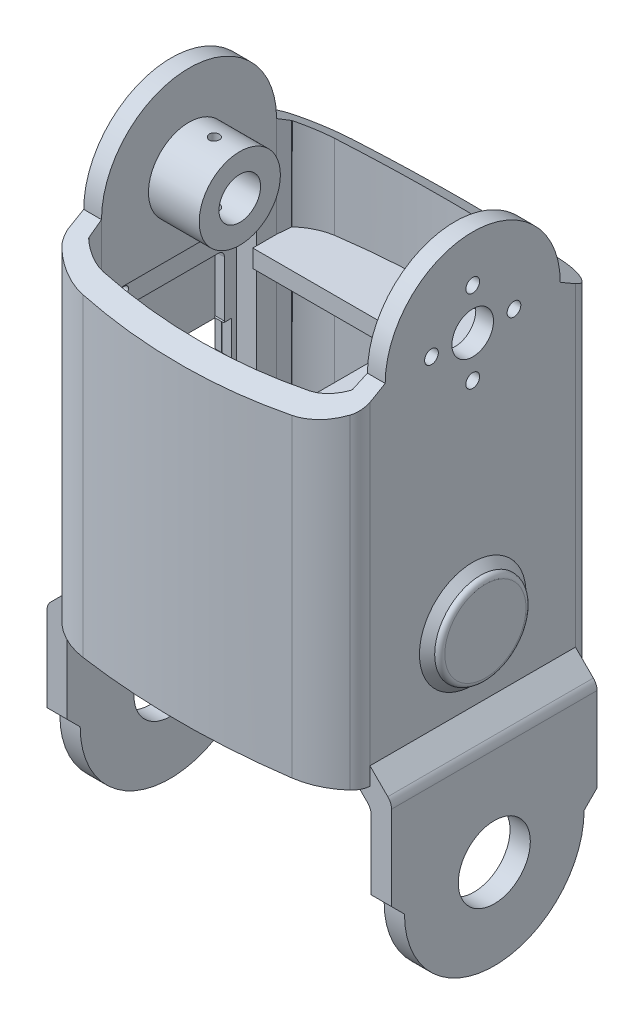
SolidWorks part; units mm, degrees
material "PLA"
ref_plane "Front Plane" through (0, 0, 0) normal (0, 0, 1) x (1, 0, 0)
ref_plane "Top Plane" through (0, 0, 0) normal (0, 1, 0) x (1, 0, 0)
ref_plane "Right Plane" through (0, 0, 0) normal (1, 0, 0) x (0, 0, -1)
sketch "Sketch1" plane through (0, 0, 0) normal (1, 0, 0) x (0, 0, -1)
  line L0 (-17.25, 0) -> (-17.25, -67.25)
  line L1 (17.25, 0) -> (17.25, -67.25)
  line L2 (-17.25, -67.25) -> (17.25, -67.25)
  arc A0 (17.25, 0) -> (-17.25, 0) centre (0, 0) ccw
  circle A1 centre (0, 0) radius 4.1
  circle A2 centre (0, 0) radius 8.125 construction
  circle A3 centre (0, 8.125) radius 1.35
  circle A4 centre (8.125, 0) radius 1.35
  circle A5 centre (-8.125, 0) radius 1.35
  circle A6 centre (0, -8.125) radius 1.35
  dimension "D1" = 34.5
  dimension "D4" = 8.2
  dimension "D5" = 16.25
  dimension "D6" = 2.7
  dimension "D2" = 67.25
  dimension "D3" = 67.25
extrude "Boss-Extrude1" add sketch "Sketch1" along normal blind 3.5
ref_plane "Plane1" through (0, 0, 0) normal (0, -1, 0) x (-1, 0, 0)
ref_plane "Plane2" through (29.7, 0, 0) normal (-1, 0, 0) x (0, 0, 1)
sketch "Sketch2" plane through (0, 0, 0) normal (0, -1, 0) x (-1, 0, 0)
  line L0 (0, -17.25) -> (-59.4, -17.25) construction
  line L1 (-29.7, 0) -> (-29.7, -28) construction
  line L3 (-59.4, -17.25) -> (-59.4, -20.25)
  line L4 (0, -17.25) -> (0, -20.25)
  line L6 (-29.7, -28) -> (-17.6897, -27.7644) construction
  line L7 (-17.6897, -27.7644) -> (-9.1109, -26.529) construction
  line L8 (-9.1109, -26.529) -> (-3.2086, -24.1613) construction
  line L9 (-3.2086, -24.1613) -> (-1.3201, -22.8861) construction
  line L10 (-1.3201, -22.8861) -> (-0.3051, -21.5079) construction
  line L11 (-0.3051, -21.5079) -> (-0.1375, -21.1541) construction
  line L12 (-0.1375, -21.1541) -> (0, -20.25) construction
  line L13 (-3.5, -17.25) -> (-3.7359, -19.9547)
  line L14 (-55.9, -17.25) -> (-55.6641, -19.9547)
  line L15 (-55.9, -17.25) -> (-59.4, -17.25)
  line L17 (0, -17.25) -> (-3.5, -17.25)
  arc A0 (0, -20.25) -> (-1.3201, -22.8861) centre (-4.0147, -19.8881) cw
  arc A1 (-1.3201, -22.8861) -> (-9.1109, -26.529) centre (-11.2153, -11.8765) cw
  arc A2 (-29.7, -28) -> (-9.1109, -26.529) centre (-29.7, 116.8281) ccw
  arc A3 (-29.7, -24.2523) -> (-9.3648, -22.779) centre (-29.7, 116.8281) ccw
  arc A4 (-3.8286, -20.1061) -> (-9.3648, -22.779) centre (-11.2153, -11.8765) cw
  arc A5 (-3.7359, -19.9547) -> (-3.8286, -20.1061) centre (-4.0147, -19.8881) cw
  arc A6 (-29.7, -28) -> (-50.2891, -26.529) centre (-29.7, 116.8281) cw
  arc A7 (-58.0799, -22.8861) -> (-50.2891, -26.529) centre (-48.1847, -11.8765) ccw
  arc A8 (-59.4, -20.25) -> (-58.0799, -22.8861) centre (-55.3853, -19.8881) ccw
  arc A9 (-55.6641, -19.9547) -> (-55.5714, -20.1061) centre (-55.3853, -19.8881) ccw
  arc A10 (-55.5714, -20.1061) -> (-50.0352, -22.779) centre (-48.1847, -11.8765) ccw
  arc A11 (-29.7, -24.2523) -> (-50.0352, -22.779) centre (-29.7, 116.8281) cw
  dimension "D1" = 59.4
extrude "Boss-Extrude2" add sketch "Sketch2" along normal blind 67.25
mirror "Mirror2" about plane through (29.7, 0, 0) normal (-1, 0, 0) of "Boss-Extrude1"
sketch "Sketch3" plane through (0, 0, 0) normal (-1, 0, 0) x (0, 0, 1)
  line L0 (17.25, 0) -> (32.7486, -8.9481)
  line L1 (-1.925, 0) -> (1.925, 0) construction
  line L2 (32.7486, -8.9481) -> (32.7486, 0)
  line L3 (32.7486, 0) -> (17.25, 0)
  arc A0 (17.25, 0) -> (-17.25, 0) centre (0, 0) ccw construction
  dimension "D1" = 30
extrude "Cut-Extrude1" cut sketch "Sketch3" against normal through all
ref_plane "Plane3" through (0, 0, 0) normal (0, 0, -1) x (-1, 0, 0)
mirror "Mirror3" about plane through (0, 0, 0) normal (0, 0, -1) of "Cut-Extrude1", "Boss-Extrude2"
sketch "Sketch4" plane through (0, 0, 0) normal (-1, 0, 0) x (0, 0, 1)
  line L0 (-20.25, -67.25) -> (-20.25, -1.7321) construction
  line L1 (-13.25, -13.5) -> (13.25, -13.5)
  line L2 (-13.25, -13.5) -> (-13.25, -60.75)
  line L3 (-13.25, -60.75) -> (13.25, -60.75)
  line L4 (13.25, -13.5) -> (13.25, -60.75)
  line L5 (20.25, -67.25) -> (20.25, -1.7321) construction
  line L6 (20.25, -67.25) -> (-20.25, -67.25) construction
  dimension "D1" = 7
  dimension "D2" = 7
  dimension "D3" = 13.5
  dimension "D4" = 6.5
extrude "Cut-Extrude2" cut sketch "Sketch4" against normal blind 3.5
sketch "Sketch6" plane through (0, 0, 0) normal (-1, 0, 0) x (0, 0, 1)
  line L8 (-15.75, -63.25) -> (15.75, -63.25)
  line L9 (-15.75, -11) -> (-15.75, -63.25)
  line L10 (15.75, -63.25) -> (15.75, -11)
  line L11 (15.75, -11) -> (-15.75, -11)
  line L12 (-15.75, -63.25) -> (15.75, -63.25)
  line L13 (-15.75, -11) -> (-15.75, -63.25)
  line L14 (15.75, -63.25) -> (15.75, -11)
  line L15 (15.75, -11) -> (-15.75, -11)
  dimension "D1" = 2.5
extrude "Boss-Extrude3" add sketch "Sketch6" along normal blind 2
chamfer "Chamfer2" distance 2 angle 45 4 edges at (-2, -63.25, 0) (-2, -37.125, 15.75) (-2, -37.125, -15.75) (-2, -11, 0)
sketch "Sketch7" plane through (0, 0, 0) normal (1, 0, 0) x (0, 0, -1)
  line L4 (-13.25, -60.75) -> (13.25, -60.75)
  line L5 (13.25, -60.75) -> (13.25, -13.5)
  line L6 (13.25, -13.5) -> (-13.25, -13.5)
  line L7 (-13.25, -13.5) -> (-13.25, -60.75)
  line L8 (-13.25, -60.75) -> (13.25, -60.75)
  line L9 (13.25, -60.75) -> (13.25, -13.5)
  line L10 (13.25, -13.5) -> (-13.25, -13.5)
  line L11 (-13.25, -13.5) -> (-13.25, -60.75)
  dimension "D1" = 0
extrude "Cut-Extrude3" cut sketch "Sketch7" against normal blind 0.8
sketch "Sketch8" plane through (-2, 0, 0) normal (-1, 0, 0) x (0, 0, 1)
  line L0 (15.75, -63.25) -> (15.75, -11) construction
  line L1 (-10.6511, -32.25) -> (10.75, -32.25)
  line L2 (-10.6511, -32.25) -> (-10.6511, -38.75)
  line L3 (-10.6511, -38.75) -> (10.75, -38.75)
  line L4 (10.75, -32.25) -> (10.75, -38.75)
  line L5 (-15.75, -11) -> (-15.75, -63.25) construction
  line L6 (15.75, -11) -> (-15.75, -11) construction
  line L7 (-15.75, -63.25) -> (15.75, -63.25) construction
  dimension "D1" = 5
  dimension "D2" = 5.0989
  dimension "D3" = 21.25
  dimension "D4" = 24.5
extrude "Cut-Extrude4" cut sketch "Sketch8" against normal up to next
sketch "Sketch9" plane through (59.4, 0, 0) normal (1, 0, 0) x (0, 0, -1)
  circle A0 centre (0, -49.64) radius 7.1
  dimension "D1" = 14.2
extrude "Cut-Extrude5" cut sketch "Sketch9" against normal up to next
ref_plane "Plane4" through (0, -19.75, 0) normal (0, -1, 0) x (-1, 0, 0)
sketch "Sketch10" plane through (0, -19.75, 0) normal (0, -1, 0) x (-1, 0, 0)
  line L0 (-55.6641, -19.9547) -> (-55.9, -17.25) construction
  line L1 (-3.5, -17.25) -> (-3.7359, -19.9547) construction
  line L3 (-3.5, -17.25) -> (-3.5, 17.25) construction
  line L6 (-3.5, 17.25) -> (-3.7359, 19.9547) construction
  line L7 (-55.9, -17.25) -> (-55.9, 17.25) construction
  line L8 (-55.6641, 19.9547) -> (-55.9, 17.25) construction
  line L9 (-55.6641, -19.9547) -> (-55.9, -17.25)
  line L10 (-3.5, -17.25) -> (-3.7359, -19.9547)
  line L11 (-3.5, -17.25) -> (-3.5, -12.56)
  line L12 (-3.5, 17.25) -> (-3.7359, 19.9547)
  line L13 (-55.9, -17.25) -> (-55.9, 17.25)
  line L14 (-55.6641, 19.9547) -> (-55.9, 17.25)
  line L15 (-18.2613, -12.36) -> (-18.2613, -12.56) construction
  line L16 (-12.72, -12.36) -> (-25.62, -12.36) construction
  line L17 (-3.5, -12.56) -> (-34.52, -12.56)
  line L18 (-34.52, -12.56) -> (-34.52, 12.56)
  line L19 (-3.5, 12.56) -> (-3.5, 17.25)
  line L43 (-34.52, 12.56) -> (-3.5, 12.56)
  line L45 (-25.62, 12.36) -> (-12.72, 12.36) construction
  line L46 (-34.52, 5) -> (-34.52, 13.1992) construction
  line L47 (-31.62, 5) -> (-35.82, 5) construction
  line L48 (-34.32, 6.7) -> (-34.32, 5.6557) construction
  arc A0 (-55.6641, -19.9547) -> (-55.5714, -20.1061) centre (-55.3853, -19.8881) ccw construction
  arc A1 (-50.0352, -22.779) -> (-9.3648, -22.779) centre (-29.7, 116.8281) ccw construction
  arc A2 (-55.5714, -20.1061) -> (-50.0352, -22.779) centre (-48.1847, -11.8765) ccw construction
  arc A3 (-9.3648, -22.779) -> (-3.8286, -20.1061) centre (-11.2153, -11.8765) ccw construction
  arc A4 (-3.8286, -20.1061) -> (-3.7359, -19.9547) centre (-4.0147, -19.8881) ccw construction
  arc A5 (-3.7359, 19.9547) -> (-3.8286, 20.1061) centre (-4.0147, 19.8881) ccw construction
  arc A6 (-3.8286, 20.1061) -> (-9.3648, 22.779) centre (-11.2153, 11.8765) ccw construction
  arc A7 (-9.3648, 22.779) -> (-50.0352, 22.779) centre (-29.7, -116.8281) ccw construction
  arc A8 (-55.5714, 20.1061) -> (-55.6641, 19.9547) centre (-55.3853, 19.8881) ccw construction
  arc A9 (-50.0352, 22.779) -> (-55.5714, 20.1061) centre (-48.1847, 11.8765) ccw construction
  arc A30 (-55.6641, -19.9547) -> (-55.5714, -20.1061) centre (-55.3853, -19.8881) ccw
  arc A31 (-50.0352, -22.779) -> (-9.3648, -22.779) centre (-29.7, 116.8281) ccw
  arc A32 (-55.5714, -20.1061) -> (-50.0352, -22.779) centre (-48.1847, -11.8765) ccw
  arc A33 (-9.3648, -22.779) -> (-3.8286, -20.1061) centre (-11.2153, -11.8765) ccw
  arc A34 (-3.8286, -20.1061) -> (-3.7359, -19.9547) centre (-4.0147, -19.8881) ccw
  arc A35 (-3.7359, 19.9547) -> (-3.8286, 20.1061) centre (-4.0147, 19.8881) ccw
  arc A36 (-3.8286, 20.1061) -> (-9.3648, 22.779) centre (-11.2153, 11.8765) ccw
  arc A37 (-9.3648, 22.779) -> (-50.0352, 22.779) centre (-29.7, -116.8281) ccw
  arc A38 (-55.5714, 20.1061) -> (-55.6641, 19.9547) centre (-55.3853, 19.8881) ccw
  arc A39 (-50.0352, 22.779) -> (-55.5714, 20.1061) centre (-48.1847, 11.8765) ccw
  dimension "D1" = 0.2
  dimension "D2" = 0.2
  dimension "D3" = 0.2
extrude "Boss-Extrude4" add sketch "Sketch10" along normal blind 3.5
sketch "Sketch11" plane through (0, -23.25, 0) normal (0, -1, 0) x (-1, 0, 0)
  line L0 (-36.07, -6.9) -> (-40.07, -6.9) construction
  line L2 (-36.07, -6.9) -> (-36.07, -24.1084) construction
  line L3 (-40.07, -6.9) -> (-40.07, -24.1084) construction
  line L5 (-36.07, -24.1084) -> (-40.07, -24.1084)
  line L6 (-36.07, -24.1084) -> (-36.07, 25.609)
  line L7 (-36.07, 25.609) -> (-40.07, 25.609)
  line L8 (-40.07, -24.1084) -> (-40.07, 25.609)
  arc A0 (-50.0352, -22.779) -> (-9.3648, -22.779) centre (-29.7, 116.8281) ccw construction
  dimension "D1" = 4
extrude "Boss-Extrude5" add sketch "Sketch11" along normal blind 40
sketch "Sketch12" plane through (40.07, 0, 0) normal (1, 0, 0) x (0, 0, -1)
  circle A0 centre (0, -49.64) radius 7.1
extrude "Cut-Extrude6" cut sketch "Sketch12" against normal blind 10
chamfer "Chamfer3" distance 1 angle 45 1 edges at (36.07, -23.25, 0)
chamfer "Chamfer4" distance 1 angle 45 1 edges at (40.07, -23.25, 0)
fillet "Fillet1" radius 3 2 edges at (38.0708, -63.25, -24.0037) (38.0708, -63.25, 24.0037)
sketch "Sketch13" plane through (59.4, 0, 0) normal (1, 0, 0) x (0, 0, -1)
  circle A0 centre (0, -49.64) radius 9
  circle A1 centre (0, -49.64) radius 5.5
  dimension "D1" = 18
  dimension "D2" = 11
extrude "Boss-Extrude6" add sketch "Sketch13" along normal blind 1.5
sketch "Sketch16" plane through (60.9, 0, 0) normal (1, 0, 0) x (0, 0, -1)
  circle A0 centre (0, -49.64) radius 9
extrude "Boss-Extrude7" add sketch "Sketch16" along normal blind 1
fillet "Fillet2" radius 1 1 edges at (61.9, -49.64, -9)
ref_plane "Plane5" through (0, 0, 20.25) normal (0, 0, -1) x (-1, 0, 0)
sketch "Sketch17" plane through (0, 0, 20.25) normal (0, 0, -1) x (-1, 0, 0)
  line L0 (-59.4, -67.25) -> (-55.9, -67.25) construction
  line L1 (-59.4, -67.25) -> (-59.4, -70.75) construction
  line L3 (-55.9, -67.25) -> (-59.4, -70.75) construction
  line L4 (-59.4, -67.25) -> (-59.65, -67.25) construction
  line L5 (-59.4, -70.75) -> (-59.65, -71) construction
  line L6 (-59.65, -71) -> (-59.65, -105.91) construction
  line L7 (-59.4, -67.25) -> (-59.4, -63.75) construction
  line L8 (-59.4, -63.75) -> (-64.5645, -68.9145) construction
  line L9 (-59.65, -105.91) -> (-63.15, -105.91)
  line L10 (-63.15, -105.91) -> (-63.15, -67.5)
  line L11 (-63.15, -67.5) -> (-59.4, -63.75)
  line L12 (-59.4, -63.75) -> (-59.4, -67.25)
  line L13 (-59.4, -67.25) -> (-55.9, -67.25)
  line L14 (-55.9, -67.25) -> (-59.65, -71)
  line L15 (-59.65, -71) -> (-59.65, -105.91)
  dimension "D1" = 3.5
  dimension "D2" = 3.5
  dimension "D3" = 0.25
  dimension "D4" = 3.5
  dimension "D5" = 45
  dimension "D6" = 3.5
sketch "Sketch18" plane through (55.9, 0, 0) normal (-1, 0, 0) x (0, 0, 1)
  circle A0 centre (0, -49.64) radius 9
  circle A1 centre (0, -49.64) radius 7.1
  circle A2 centre (0, -49.64) radius 7.1
  dimension "D2" = 18
  dimension "D1" = 0
extrude "Boss-Extrude8" add sketch "Sketch18" along normal blind 0.5
chamfer "Chamfer5" distance 0.5 angle 45 1 edges at (55.9, -49.64, 9)
extrude "Boss-Extrude9" add sketch "Sketch17" along normal blind 40.5
sketch "Sketch19" plane through (63.15, 0, 0) normal (1, 0, 0) x (0, 0, -1)
  line L0 (-17.7, -88.21) -> (-20.25, -85.66)
  line L1 (-20.25, -85.66) -> (-20.25, -105.91)
  line L2 (20.25, -105.91) -> (-20.25, -105.91) construction
  line L3 (0, -105.91) -> (0, -88.21) construction
  line L4 (-20.25, -67.5) -> (-20.25, -105.91) construction
  line L5 (17.7, -88.21) -> (20.25, -85.66)
  line L6 (-20.25, -105.91) -> (0, -105.91)
  line L7 (20.25, -67.5) -> (20.25, -105.91) construction
  line L8 (0, -105.91) -> (20.25, -105.91)
  line L9 (20.25, -105.91) -> (20.25, -85.66)
  arc A0 (-17.7, -88.21) -> (17.7, -88.21) centre (0, -88.21) ccw
  line M5 (-20.25, -67.5) -> (-20.25, -105.91)
  line M6 (-20.25, -105.91) -> (20.25, -105.91)
  line M7 (20.25, -105.91) -> (20.25, -67.5)
  dimension "D1" = 17.7
  dimension "D2" = 45
  dimension "D3" = 45
extrude "Cut-Extrude8" cut sketch "Sketch19" against normal up to next contours A0 L0 M5 M6 | A0 L5 M6 M7
chamfer "Chamfer6" distance 1.5 angle 45 1 edges at (59.4, -49.64, 9)
sketch "Sketch20" plane through (63.15, 0, 0) normal (1, 0, 0) x (0, 0, -1)
  line L0 (0, -49.64) -> (0, -88.21) construction
  circle A0 centre (0, -88.21) radius 7.1
  dimension "D2" = 14.2
  dimension "D1" = 38.57
extrude "Cut-Extrude9" cut sketch "Sketch20" against normal up to next
sketch "Sketch21" plane through (0, 0, 0) normal (-1, 0, 0) x (0, 0, 1)
  circle A0 centre (0, 8.125) radius 1.5
  circle A1 centre (8.125, 0) radius 1.5
  circle A2 centre (0, -8.125) radius 1.5
  circle A3 centre (-8.125, 0) radius 1.5
  dimension "D1" = 3
extrude "Boss-Extrude10" add sketch "Sketch21" against normal blind 3.5
mirror "Mirror4" about plane through (29.7, 0, 0) normal (-1, 0, 0) of "Cut-Extrude9", "Cut-Extrude8", "Boss-Extrude9"
sketch "Sketch22" plane through (-2, 0, 0) normal (-1, 0, 0) x (0, 0, 1)
  circle A0 centre (0, -49.64) radius 3.75
  dimension "D1" = 7.5
extrude "Cut-Extrude10" cut sketch "Sketch22" against normal up to next
sketch "Sketch23" plane through (-0.8, 0, 0) normal (1, 0, 0) x (0, 0, -1)
  line L65 (10.8, -38.89) -> (7, -38.89)
  line L66 (10.8, -32.115) -> (10.8, -38.89)
  line L67 (9.303, -32.115) -> (10.8, -32.115)
  line L68 (9.4423, -31.8921) -> (9.303, -32.115)
  line L69 (9.4423, -20.9369) -> (9.4423, -31.8921)
  line L70 (-8.2423, -19.7369) -> (8.2423, -19.7369)
  line L71 (-9.4423, -31.8921) -> (-9.4423, -20.9369)
  line L72 (-9.303, -32.115) -> (-9.4423, -31.8921)
  line L73 (-10.8, -32.115) -> (-9.303, -32.115)
  line L74 (-10.8, -38.89) -> (-10.8, -32.115)
  line L75 (-7, -38.89) -> (-10.8, -38.89)
  line L76 (-7, -40.6536) -> (-7, -38.89)
  line L77 (-11.36, -43.6785) -> (-9.7065, -43.6785)
  line L78 (-11.86, -16.5298) -> (-11.86, -43.1785)
  line L79 (10.3601, -15.03) -> (-10.3604, -15.03)
  line L80 (11.86, -43.1784) -> (11.86, -16.5295)
  line L81 (9.7065, -43.6785) -> (11.36, -43.6785)
  line L82 (7, -38.89) -> (7, -40.6536)
  line L83 (10.8, -38.89) -> (7, -38.89)
  line L84 (10.8, -32.115) -> (10.8, -38.89)
  line L85 (9.303, -32.115) -> (10.8, -32.115)
  line L86 (9.4423, -31.8921) -> (9.303, -32.115)
  line L87 (9.4423, -20.9369) -> (9.4423, -31.8921)
  line L88 (-8.2423, -19.7369) -> (8.2423, -19.7369)
  line L89 (-9.4423, -31.8921) -> (-9.4423, -20.9369)
  line L90 (-9.303, -32.115) -> (-9.4423, -31.8921)
  line L91 (-10.8, -32.115) -> (-9.303, -32.115)
  line L92 (-10.8, -38.89) -> (-10.8, -32.115)
  line L93 (-7, -38.89) -> (-10.8, -38.89)
  line L94 (-7, -40.6536) -> (-7, -38.89)
  line L95 (-11.36, -43.6785) -> (-9.7065, -43.6785)
  line L96 (-11.86, -16.5298) -> (-11.86, -43.1785)
  line L97 (10.3601, -15.03) -> (-10.3604, -15.03)
  line L98 (11.86, -43.1784) -> (11.86, -16.5295)
  line L99 (9.7065, -43.6785) -> (11.36, -43.6785)
  line L100 (7, -38.89) -> (7, -40.6536)
  arc A34 (-10.25, -40.54) -> (-10.25, -42.14) centre (-10.25, -41.34) ccw construction
  arc A35 (-10.25, -42.14) -> (-10.25, -40.54) centre (-10.25, -41.34) ccw construction
  arc A36 (-10.25, -16.09) -> (-10.25, -17.69) centre (-10.25, -16.89) ccw construction
  arc A37 (-10.25, -17.69) -> (-10.25, -16.09) centre (-10.25, -16.89) ccw construction
  arc A38 (10.25, -16.09) -> (10.25, -17.69) centre (10.25, -16.89) ccw construction
  arc A39 (10.25, -17.69) -> (10.25, -16.09) centre (10.25, -16.89) ccw construction
  arc A40 (9.4423, -20.9369) -> (8.2423, -19.7369) centre (8.2423, -20.9369) ccw
  arc A41 (-8.2423, -19.7369) -> (-9.4423, -20.9369) centre (-8.2423, -20.9369) ccw
  arc A42 (-7, -40.6536) -> (-9.7065, -43.6785) centre (0, -49.64) ccw
  arc A43 (-11.86, -43.1785) -> (-11.36, -43.6785) centre (-11.36, -43.1785) ccw
  arc A44 (11.36, -43.6785) -> (11.86, -43.1784) centre (11.36, -43.1785) ccw
  arc A45 (9.7065, -43.6785) -> (7, -40.6536) centre (0, -49.64) ccw
  arc A46 (9.4423, -20.9369) -> (8.2423, -19.7369) centre (8.2423, -20.9369) ccw
  arc A47 (-8.2423, -19.7369) -> (-9.4423, -20.9369) centre (-8.2423, -20.9369) ccw
  arc A48 (-7, -40.6536) -> (-9.7065, -43.6785) centre (0, -49.64) ccw
  arc A49 (-11.86, -43.1785) -> (-11.36, -43.6785) centre (-11.36, -43.1785) ccw
  arc A50 (11.36, -43.6785) -> (11.86, -43.1784) centre (11.36, -43.1785) ccw
  arc A51 (9.7065, -43.6785) -> (7, -40.6536) centre (0, -49.64) ccw
  arc A52 (10.25, -42.14) -> (10.25, -40.54) centre (10.25, -41.34) ccw construction
  arc A53 (10.25, -40.54) -> (10.25, -42.14) centre (10.25, -41.34) ccw construction
  arc A54 (-10.25, -40.54) -> (-10.25, -42.14) centre (-10.25, -41.34) ccw
  arc A55 (-10.25, -42.14) -> (-10.25, -40.54) centre (-10.25, -41.34) ccw
  arc A56 (-10.25, -16.09) -> (-10.25, -17.69) centre (-10.25, -16.89) ccw
  arc A57 (-10.25, -17.69) -> (-10.25, -16.09) centre (-10.25, -16.89) ccw
  arc A58 (10.25, -16.09) -> (10.25, -17.69) centre (10.25, -16.89) ccw
  arc A59 (10.25, -17.69) -> (10.25, -16.09) centre (10.25, -16.89) ccw
  arc A60 (10.25, -42.14) -> (10.25, -40.54) centre (10.25, -41.34) ccw
  arc A61 (10.25, -40.54) -> (10.25, -42.14) centre (10.25, -41.34) ccw
  spline S4 degree 3 poles (532.7218, -2965.2554) (46.0734, -186.7644) (2.6461, -12.4021) (-10.7484, -15.0781) (-10.8437, -15.1068) (-11.0252, -15.182) (-11.1112, -15.2282) (-11.2742, -15.337) (-11.3514, -15.4001) (-11.5587, -15.6075) (-11.6705, -15.7746) (-16.0328, -26.295) (93.5141, -90.5306) (1392.4975, 2631.509) knots -17.228517 -17.228517 -17.228517 -17.228517 0.125 0.125 0.25 0.25 0.375 0.375 0.5 0.5 0.75 0.75 15.088906 15.088906 15.088906 15.088906 only from (-10.3604, -15.03) to (-11.86, -16.5298)
  spline S5 degree 3 poles (-2938.3132, -559.6797) (-159.8816, -72.9698) (14.4883, -29.5363) (11.8119, -16.1415) (11.7831, -16.0463) (11.708, -15.8648) (11.6618, -15.7788) (11.553, -15.6158) (11.4898, -15.5386) (11.2825, -15.3312) (11.1153, -15.2194) (0.5947, -10.8574) (-63.6396, -120.4095) (2658.5366, -1419.1506) knots -17.228977 -17.228977 -17.228977 -17.228977 0.125 0.125 0.25 0.25 0.375 0.375 0.5 0.5 0.75 0.75 15.089089 15.089089 15.089089 15.089089 only from (11.86, -16.5295) to (10.3601, -15.03)
  spline S6 degree 3 poles (-10.3604, -15.03) (-10.4595, -15.0298) (-10.5568, -15.0398) (-10.7484, -15.0781) (-10.8437, -15.1068) (-11.0252, -15.182) (-11.1112, -15.2282) (-11.2742, -15.337) (-11.3514, -15.4001) (-11.5587, -15.6075) (-11.6705, -15.7746) (-11.82, -16.1352) (-11.8602, -16.3318) (-11.86, -16.5298) knots 0 0 0 0 0.125 0.125 0.25 0.25 0.375 0.375 0.5 0.5 0.75 0.75 1 1 1 1
  spline S7 degree 3 poles (11.86, -16.5295) (11.8602, -16.4305) (11.8502, -16.3331) (11.8119, -16.1415) (11.7831, -16.0463) (11.708, -15.8648) (11.6618, -15.7788) (11.553, -15.6158) (11.4898, -15.5386) (11.2825, -15.3312) (11.1153, -15.2194) (10.7548, -15.0699) (10.5581, -15.0298) (10.3601, -15.03) knots 0 0 0 0 0.125 0.125 0.25 0.25 0.375 0.375 0.5 0.5 0.75 0.75 1 1 1 1
  dimension "D1" = 0.2
extrude "Boss-Extrude11" add sketch "Sketch23" along normal offset from surface (1.82 mm away) 0.2
sketch "Sketch24" plane through (36.07, 0, 0) normal (-1, 0, 0) x (0, 0, 1)
  line L1 (-13, -29.275) -> (-8, -29.275)
  line L2 (-13, -29.275) -> (-13, -45.2091)
  line L3 (-13, -45.2091) -> (-8, -45.2091)
  line L4 (-8, -29.275) -> (-8, -45.2091)
  line L5 (8, -29.275) -> (13, -29.275)
  line L6 (8, -29.275) -> (8, -45.2091)
  line L7 (8, -45.2091) -> (13, -45.2091)
  line L8 (13, -29.275) -> (13, -45.2091)
  arc A1 (10.25, -42.14) -> (10.25, -40.54) centre (10.25, -41.34) ccw construction
  arc A2 (10.25, -40.54) -> (10.25, -42.14) centre (10.25, -41.34) ccw construction
  arc A3 (-10.25, -42.14) -> (-10.25, -40.54) centre (-10.25, -41.34) ccw construction
  arc A4 (-10.25, -40.54) -> (-10.25, -42.14) centre (-10.25, -41.34) ccw construction
  arc A5 (10.25, -42.14) -> (10.25, -40.54) centre (10.25, -41.34) ccw
  arc A6 (10.25, -40.54) -> (10.25, -42.14) centre (10.25, -41.34) ccw
  arc A7 (-10.25, -42.14) -> (-10.25, -40.54) centre (-10.25, -41.34) ccw
  arc A8 (-10.25, -40.54) -> (-10.25, -42.14) centre (-10.25, -41.34) ccw
  dimension "D1" = 5
  dimension "D2" = 13
  dimension "D3" = 13
  dimension "D4" = 5
extrude "Boss-Extrude12" add sketch "Sketch24" along a picked direction on the side of the normal up to next (2.65 mm away) contours L4 L1 L2 L3 A8 A7 | L8 L5 L6 L7 A6 A5
sketch "Sketch25" plane through (36.07, 0, 0) normal (-1, 0, 0) x (0, 0, 1)
  circle A0 centre (10.25, -41.34) radius 0.8 construction
  circle A1 centre (-10.25, -41.34) radius 0.8 construction
  circle A2 centre (10.25, -41.34) radius 0.8
  circle A3 centre (-10.25, -41.34) radius 0.8
extrude "Cut-Extrude11" cut sketch "Sketch25" against normal up to next
sketch "Sketch26" plane through (0, 0, 0) normal (-1, 0, 0) x (0, 0, 1)
  circle A1 centre (0, 0) radius 13.375
  dimension "D1" = 26.75
extrude "Cut-Extrude12" cut sketch "Sketch26" along normal blind 3.3
sketch "Sketch27" plane through (-2, 0, 0) normal (-1, 0, 0) x (0, 0, 1)
  circle A0 centre (0, -49.64) radius 5
  dimension "D1" = 10
extrude "Boss-Extrude13" add sketch "Sketch27" along normal blind 1
fillet "Fillet7" radius 0.75 1 edges at (-3, -49.64, 5)
sketch "Sketch28" plane through (3.5, 0, 0) normal (1, 0, 0) x (0, 0, -1)
  circle A0 centre (0, 0) radius 4.1
  circle A1 centre (0, 0) radius 8
  dimension "D1" = 8.2
  dimension "D2" = 16
extrude "Boss-Extrude14" add sketch "Sketch28" along normal blind 1.5
sketch "Sketch29" plane through (5, 0, 0) normal (1, 0, 0) x (0, 0, -1)
  circle A0 centre (0, 0) radius 4.1
  circle A1 centre (0, 0) radius 8
  dimension "D1" = 8.2
  dimension "D2" = 16
extrude "Boss-Extrude15" add sketch "Sketch29" along normal blind 8.5
sketch "Sketch30" plane through (0, 0, 0) normal (0, -1, 0) x (-1, 0, 0)
  line L0 (-13.5, 0) -> (-3.5, 0) construction
  line L1 (-13.5, 8) -> (-13.5, -8) construction
  circle A0 centre (-8.5, 0) radius 1
  dimension "D2" = 2
  dimension "D1" = 10
extrude "Cut-Extrude13" cut sketch "Sketch30" against normal through all and the other way blind 15
sketch "Sketch31" plane through (-3.75, 0, 0) normal (-1, 0, 0) x (0, 0, 1)
  line L5 (-20.25, -85.66) -> (-17.7, -88.21)
  line L6 (17.7, -88.21) -> (20.25, -85.66)
  line L7 (20.25, -85.66) -> (20.25, -67.5)
  line L8 (20.25, -67.5) -> (-20.25, -67.5)
  line L9 (-20.25, -67.5) -> (-20.25, -85.66)
  line L10 (-20.25, -85.66) -> (-17.7, -88.21)
  line L11 (17.7, -88.21) -> (20.25, -85.66)
  line L12 (20.25, -85.66) -> (20.25, -67.5)
  line L13 (20.25, -67.5) -> (-20.25, -67.5)
  line L14 (-20.25, -67.5) -> (-20.25, -85.66)
  circle A0 centre (0, -88.21) radius 7.1 construction
  arc A1 (-17.7, -88.21) -> (17.7, -88.21) centre (0, -88.21) ccw
  arc A2 (-17.7, -88.21) -> (17.7, -88.21) centre (0, -88.21) ccw
  circle A3 centre (0, -88.21) radius 7.1
  circle M7 centre (0, -88.21) radius 7.1
  line M8 (-20.25, -85.66) -> (-17.7, -88.21)
  arc M9 (-17.7, -88.21) -> (17.7, -88.21) centre (0, -88.21) ccw
  line M10 (17.7, -88.21) -> (20.25, -85.66)
  line M11 (20.25, -85.66) -> (20.25, -67.5)
  line M12 (20.25, -67.5) -> (-20.25, -67.5)
  line M13 (-20.25, -67.5) -> (-20.25, -85.66)
  dimension "D1" = 0
extrude "Boss-Extrude16" add sketch "Sketch31" along normal blind 0.5 contours M13 M8 M9 M10 M11 M12 M7
chamfer "Chamfer7" distance 0.5 angle 45 3 edges at (-4, -67.5, -20.25) (-4, -67.5, 20.25) (-4.25, -67.5, 0)
ref_plane "Plane6" through (29.7, 0, 0) normal (1, 0, 0) x (0, 0, -1)
mirror "Mirror5" about plane through (29.7, 0, 0) normal (1, 0, 0) of "Chamfer7", "Boss-Extrude16"
fillet "Fillet8" radius 2.5 4 edges at (59.65, -71, 0) (-0.25, -71, 0) (-4.25, -68, 0) (63.65, -68, 0)
